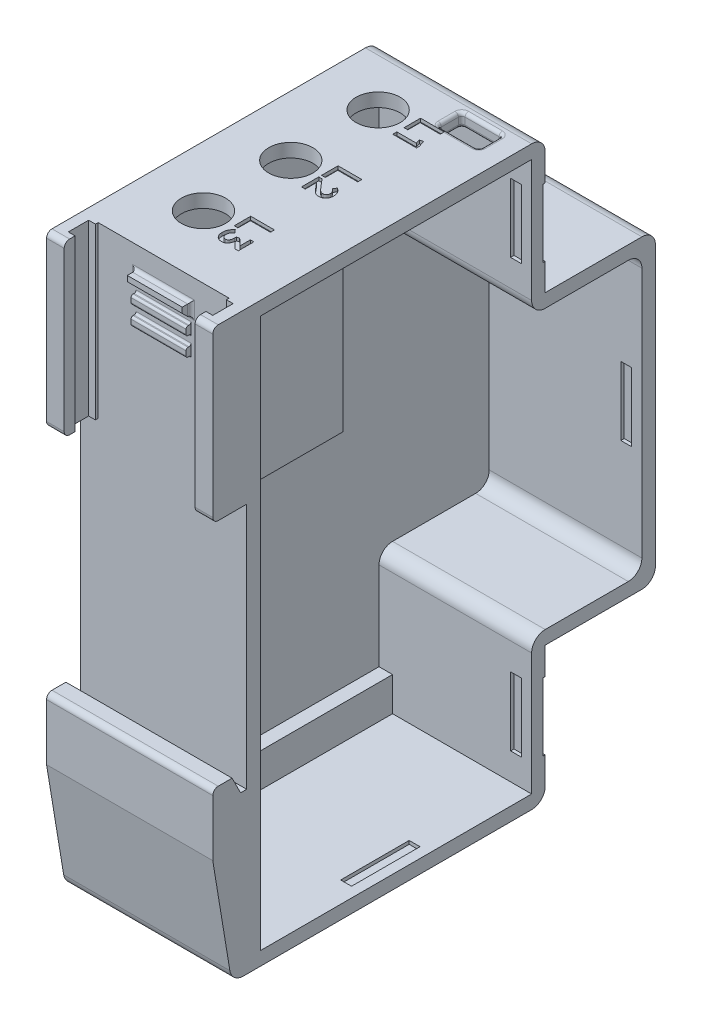
SolidWorks part; units mm, degrees
ref_plane "Front Plane" through (0, 0, 0) normal (0, 0, 1) x (1, 0, 0)
ref_plane "Top Plane" through (0, 0, 0) normal (0, 1, 0) x (1, 0, 0)
ref_plane "Right Plane" through (0, 0, 0) normal (1, 0, 0) x (0, 0, -1)
sketch "Sketch1" plane through (0, 0, 0) normal (1, 0, 0) x (0, 0, -1)
  line L0 (44, 65) -> (44, 85)
  line L1 (0, 0) -> (44, 0)
  line L2 (0, 0) -> (0, 85)
  line L3 (0, 85) -> (44, 85)
  line L4 (44, 0) -> (44, 20)
  line L5 (44, 65) -> (60.25, 65)
  line L7 (44, 20) -> (60.25, 20)
  line L8 (60.25, 65) -> (60.25, 20)
  dimension "D1" = 85
  dimension "D2" = 44
  dimension "D3" = 20
  dimension "D4" = 20
  dimension "D5" = 60.25
extrude "Boss-Extrude1" add sketch "Sketch1" along normal blind 24.5
shell "Shell1" thickness 2
sketch "Sketch2" plane through (2, 0, 0) normal (1, 0, 0) x (0, 0, -1)
  line L0 (42, 2) -> (42, 22) construction
  line L1 (42, 7) -> (12, 7)
  line L2 (42, 7) -> (42, 2)
  line L3 (42, 2) -> (12, 2)
  line L4 (12, 7) -> (12, 2)
  line L5 (2, 2) -> (42, 2) construction
  dimension "D1" = 30
  dimension "D2" = 5
extrude "Boss-Extrude2" add sketch "Sketch2" along normal blind 2
sketch "Sketch4" plane through (0, 85, 0) normal (0, 1, 0) x (1, 0, 0)
  circle A0 centre (8.86, 9.265) radius 3 construction
  circle A1 centre (8.86, 22.14) radius 3 construction
  circle A2 centre (8.86, 35.015) radius 3 construction
  circle A3 centre (8.86, 9.265) radius 3 construction
  circle A4 centre (8.86, 22.14) radius 3 construction
  circle A5 centre (8.86, 35.015) radius 3 construction
  circle A6 centre (8.86, 35.015) radius 3.25
  circle A7 centre (8.86, 22.14) radius 3.25
  circle A8 centre (8.86, 9.265) radius 3.25
  dimension "D1" = 0.25
extrude "Cut-Extrude2" cut sketch "Sketch4" against normal up to next
sketch "Sketch5" plane through (2, 0, 0) normal (1, 0, 0) x (0, 0, -1)
  line L0 (34.67, 36.04) -> (34.67, 70.24) construction
  line L1 (34.67, 64.64) -> (7.67, 64.64)
  line L2 (34.67, 64.64) -> (34.67, 41.64)
  line L3 (34.67, 41.64) -> (7.67, 41.64)
  line L4 (7.67, 64.64) -> (7.67, 41.64)
  line L5 (14.67, 70.24) -> (14.67, 36.04) construction
  point P6 (14.67, 53.14)
  point P9 (7.67, 53.14)
  dimension "D1" = 23
  dimension "D2" = 27
extrude "Boss-Extrude3" add sketch "Sketch5" along normal blind 2
sketch "Sketch6" plane through (24.5, 0, 0) normal (1, 0, 0) x (0, 0, -1)
  line L0 (0, 0) -> (-2.2, 0)
  line L1 (-2.2, 0) -> (-5, 17)
  line L2 (-5, 17) -> (-5, 26.1)
  line L3 (-5, 26.1) -> (-2.15, 26.1)
  line L4 (-2.15, 26.1) -> (-0.9, 23.6)
  line L5 (-0.9, 23.6) -> (0, 23.6)
  line L6 (0, 85) -> (0, 0) construction
  line L7 (0, 42.5) -> (-14.1034, 42.5) construction
  line L8 (0, 0) -> (44, 0) construction
  line L9 (0, 23.6) -> (0, 0)
  line L11 (44, 20) -> (58.25, 20) construction
  dimension "D1" = 5
  dimension "D2" = 6.1
  dimension "D3" = 17
  dimension "D4" = 2.2
  dimension "D5" = 2.5
  dimension "D6" = 0.9
  dimension "D7" = 2.15
extrude "Boss-Extrude4" add sketch "Sketch6" against normal up to surface (24.5 mm away) up to face at (0, 42.5, -37.0625)
sketch "Sketch7" plane through (0, 0, 0) normal (0, 0, 1) x (1, 0, 0)
  line L1 (24.5, 85) -> (21.9, 85)
  line L2 (24.5, 85) -> (24.5, 60)
  line L3 (24.5, 60) -> (21.9, 60)
  line L4 (21.9, 85) -> (21.9, 60)
  line L5 (12.25, 85) -> (12.25, 51.0538) construction
  line L6 (24.5, 85) -> (0, 85) construction
  line L7 (0, 60) -> (2.6, 60)
  line L8 (2.6, 85) -> (2.6, 60)
  line L9 (0, 85) -> (2.6, 85)
  line L10 (0, 85) -> (0, 60)
  line L11 (24.5, 65) -> (0, 65) construction
  dimension "D1" = 5
  dimension "D2" = 2.6
  dimension "D3" = 25
extrude "Boss-Extrude5" add sketch "Sketch7" along normal up to surface (5 mm away) up to face at (12.25, 21.55, 5)
sketch "Sketch8" plane through (0, 85, 0) normal (0, 1, 0) x (1, 0, 0)
  line L0 (21.9, 0) -> (2.6, 0) construction
  line L1 (22.9, -3.4) -> (1.6, -3.4)
  line L2 (22.9, -3.4) -> (22.9, -0.4)
  line L3 (22.9, -0.4) -> (1.6, -0.4)
  line L4 (1.6, -3.4) -> (1.6, -0.4)
  line L5 (2.6, -5) -> (2.6, 0) construction
  line L6 (21.9, -5) -> (21.9, 0) construction
  line L7 (24.5, -5) -> (21.9, -5) construction
  point P6 (12.25, 0)
  point P7 (12.25, -0.4)
  dimension "D1" = 0.4
  dimension "D2" = 1
  dimension "D3" = 1
  dimension "D4" = 1.6
extrude "Cut-Extrude3" cut sketch "Sketch8" against normal up to next
fillet "Fillet1" radius 2 9 edges at (12.25, 0, 2.2) (12.25, 85, -44) (12.25, 65, -60.25) (12.25, 20, -60.25) (12.25, 0, -44) (13.25, 63, -42) (13.25, 22, -42) (13.25, 63, -58.25) (13.25, 22, -58.25)
fillet "Fillet2" radius 0.8 5 edges at (12.25, 26.1, 5) (1.3, 60, 5) (23.2, 60, 5) (1.3, 85, 5) (23.2, 85, 5)
sketch "Sketch9" plane through (0, 85, 0) normal (0, 1, 0) x (1, 0, 0)
  line L0 (24.5, 42) -> (24.5, -4.2) construction
  line L1 (21.2, 41) -> (15.2, 41)
  line L2 (21.2, 41) -> (21.2, 37.5)
  line L3 (21.2, 37.5) -> (15.2, 37.5)
  line L4 (15.2, 41) -> (15.2, 37.5)
  line L5 (24.5, 42) -> (2, 42) construction
  dimension "D1" = 6
  dimension "D2" = 3.5
  dimension "D3" = 3.3
  dimension "D4" = 1
extrude "Cut-Extrude4" cut sketch "Sketch9" against normal up to next contours L2 L3 L4 L1
fillet "Fillet3" radius 0.5 12 edges at (18.2, 85, -37.5) (18.2, 83, -37.5) (18.2, 83, -41) (18.2, 85, -41) (21.2, 84, -41) (21.2, 85, -39.25) (21.2, 84, -37.5) (21.2, 83, -39.25) (15.2, 83, -39.25) (15.2, 84, -37.5) (15.2, 85, -39.25) (15.2, 84, -41)
sketch "Sketch10" plane through (0, 0, 0) normal (0, 0, 1) x (1, 0, 0)
  line L1 (16.3, 81.7) -> (8.2, 81.7)
  line L2 (16.3, 81.7) -> (16.3, 80.1)
  line L3 (16.3, 80.1) -> (8.2, 80.1)
  line L4 (8.2, 81.7) -> (8.2, 80.1)
  line L5 (21.9, 85) -> (2.6, 85) construction
  line L7 (16.5, 88.2) -> (16.5, 86.6) construction
  line L8 (18.1, 77.9) -> (6.4, 77.9) construction
  point P6 (12.25, 80.1)
  point P9 (12.25, 85)
  dimension "D1" = 2.2
  dimension "D2" = 1.6
  dimension "D3" = 0.2
extrude "Boss-Extrude6" add sketch "Sketch10" along normal offset from surface (1.3 mm away) 0.3
fillet "Fillet4" radius 0.5 4 edges at (16.3, 80.9, 0) (8.2, 80.9, 0) (12.25, 81.7, 0) (12.25, 80.1, 0)
sketch "Sketch12" plane through (0, 0, 0) normal (0, 0, 1) x (1, 0, 0)
  line L0 (6.4, 75.9) -> (18.1, 75.9) construction
  line L1 (18.1, 77.9) -> (6.4, 77.9) construction
  line L2 (8.2, 75.9) -> (16.3, 75.9) construction
  line L3 (16.3, 77.9) -> (8.2, 77.9) construction
  line L4 (16.3, 80.1) -> (16.3, 81.7) construction
  line L5 (16.3, 77.9) -> (8.2, 77.9) construction
  line L6 (16.3, 77.65) -> (16.3, 78.9)
  line L7 (16.3, 78.9) -> (8.2, 78.9)
  line L8 (8.2, 77.65) -> (8.2, 78.9)
  line L9 (16.3, 75.9) -> (8.2, 75.9) construction
  line L10 (16.3, 76.15) -> (16.3, 74.9)
  line L11 (16.3, 74.9) -> (8.2, 74.9)
  line L12 (8.2, 76.15) -> (8.2, 74.9)
  line L13 (8.2, 81.7) -> (8.2, 80.1) construction
  line L14 (16.3, 77.65) -> (8.2, 77.65)
  line L15 (8.2, 76.15) -> (16.3, 76.15)
  dimension "D1" = 1
  dimension "D2" = 1
  dimension "D3" = 0.25
extrude "Boss-Extrude7" add sketch "Sketch12" along normal blind 0.75 contours L8 L3 L6 L7 | L2 L12 L11 L10
fillet "Fillet5" radius 0.3 8 edges at (12.25, 78.9, 0) (12.25, 74.9, 0) (12.25, 74.9, 0.75) (12.25, 78.9, 0.75) (12.25, 76.15, 0) (12.25, 76.15, 0.75) (12.25, 77.65, 0) (12.25, 77.65, 0.75)
chamfer "Chamfer1" distance 0.8 angle 45 1 edges at (12.25, 80.1, 1.3)
sketch "Sketch13" plane through (0, 0, -44) normal (0, 0, -1) x (-1, 0, 0)
  line L0 (-24.5, 2) -> (-24.5, 20) construction
  line L1 (-24.5, 6) -> (-22.5, 6)
  line L2 (-24.5, 6) -> (-24.5, 16)
  line L3 (-24.5, 16) -> (-22.5, 16)
  line L4 (-22.5, 6) -> (-22.5, 16)
  line L5 (0, 2) -> (0, 20) construction
  line L6 (-12.25, 2) -> (-12.25, 83) construction
  line L7 (-24.5, 2) -> (0, 2) construction
  line L8 (0, 83) -> (-24.5, 83) construction
  line L9 (-12.25, 42.5) -> (-31.0931, 42.5) construction
  line L10 (-24.5, 69) -> (-22.5, 69)
  line L11 (-22.5, 79) -> (-22.5, 69)
  line L12 (-24.5, 79) -> (-22.5, 79)
  line L13 (-24.5, 79) -> (-24.5, 69)
  point P6 (-22.5, 11)
  point P9 (0, 11)
  dimension "D1" = 10
  dimension "D2" = 2
extrude "Cut-Extrude5" cut sketch "Sketch13" against normal blind 0.3
sketch "Sketch14" plane through (0, 0, -58.25) normal (0, 0, 1) x (1, 0, 0)
  line L0 (24.5, 24) -> (24.5, 61) construction
  line L1 (23, 47.55) -> (21.4, 47.55)
  line L2 (23, 47.55) -> (23, 37.45)
  line L3 (23, 37.45) -> (21.4, 37.45)
  line L4 (21.4, 47.55) -> (21.4, 37.45)
  point P6 (24.5, 42.5)
  point P7 (23, 42.5)
  dimension "D1" = 10.1
  dimension "D2" = 1.6
  dimension "D3" = 1.5
extrude "Cut-Extrude6" cut sketch "Sketch14" against normal blind 0.5
sketch "Sketch15" plane through (0, 0, -42) normal (0, 0, 1) x (1, 0, 0)
  line L1 (23, 79.05) -> (21.4, 79.05)
  line L2 (23, 79.05) -> (23, 68.95)
  line L3 (23, 68.95) -> (21.4, 68.95)
  line L4 (21.4, 79.05) -> (21.4, 68.95)
  line L5 (24.5, 65) -> (24.5, 83) construction
  line L6 (24.5, 83) -> (24.5, 2) construction
  line L7 (24.5, 42.5) -> (11.011, 42.5) construction
  line L8 (23, 16.05) -> (21.4, 16.05)
  line L9 (21.4, 5.95) -> (21.4, 16.05)
  line L10 (23, 5.95) -> (21.4, 5.95)
  line L11 (23, 5.95) -> (23, 16.05)
  point P6 (24.5, 74)
  point P7 (23, 74)
  dimension "D1" = 10.1
  dimension "D2" = 1.6
  dimension "D3" = 1.5
extrude "Cut-Extrude7" cut sketch "Sketch15" against normal blind 0.5
sketch "Sketch16" plane through (0, 2, 2) normal (0, 1, 0) x (1, 0, 0)
  line L1 (23, 29.05) -> (21.4, 29.05)
  line L2 (23, 29.05) -> (23, 18.95)
  line L3 (23, 18.95) -> (21.4, 18.95)
  line L4 (21.4, 29.05) -> (21.4, 18.95)
  line L5 (24.5, 4) -> (24.5, 44) construction
  point P6 (24.5, 24)
  point P7 (23, 24)
  dimension "D1" = 10.1
  dimension "D2" = 1.6
  dimension "D3" = 1.5
extrude "Cut-Extrude8" cut sketch "Sketch16" against normal blind 0.5
sketch "Sketch17" plane through (11.56, 83, -19.6102) normal (0, 1, 0) x (-1, 0, 0)
  line L1 (-9.84, 2.6602) -> (-11.44, 2.6602)
  line L2 (-9.84, 2.6602) -> (-9.84, -7.4398)
  line L3 (-9.84, -7.4398) -> (-11.44, -7.4398)
  line L4 (-11.44, 2.6602) -> (-11.44, -7.4398)
  line L5 (-12.94, -22.3898) -> (-12.94, 17.6102) construction
  point P4 (-11.44, -2.3898)
  point P8 (-12.94, -2.3898)
  dimension "D1" = 10.1
  dimension "D2" = 1.6
  dimension "D3" = 1.5
extrude "Cut-Extrude10" cut sketch "Sketch17" along normal blind 0.5
sketch "Sketch18" plane through (0, 0, -2) normal (0, 0, -1) x (-1, 0, 0)
  line L1 (-21.4, 57.6) -> (-23, 57.6)
  line L2 (-21.4, 57.6) -> (-21.4, 27.4)
  line L3 (-21.4, 27.4) -> (-23, 27.4)
  line L4 (-23, 57.6) -> (-23, 27.4)
  line L5 (-24.5, 83) -> (-24.5, 2) construction
  point P4 (-23, 42.5)
  point P8 (-24.5, 42.5)
  dimension "D1" = 30.2
  dimension "D2" = 1.6
  dimension "D3" = 1.5
extrude "Cut-Extrude11" cut sketch "Sketch18" against normal blind 0.5
sketch "Sketch19" plane through (0, 85, 0) normal (0, 1, 0) x (1, 0, 0)
  line L0 (13.0397, 38.265) -> (13.0397, 31.765) construction
  line L1 (8.86, 38.265) -> (13.0397, 38.265) construction
  line L2 (13.0397, 25.39) -> (13.0397, 18.89) construction
  line L3 (8.86, 31.765) -> (13.0397, 31.765) construction
  line L5 (8.86, 25.39) -> (13.0397, 25.39) construction
  line L6 (13.0397, 12.515) -> (13.0397, 6.015) construction
  line L7 (8.86, 18.89) -> (13.0397, 18.89) construction
  line L9 (8.86, 12.515) -> (13.0397, 12.515) construction
  line L11 (8.86, 6.015) -> (13.0397, 6.015) construction
  circle A0 centre (8.86, 35.015) radius 3.25 construction
  circle A1 centre (8.86, 22.14) radius 3.25 construction
  circle A2 centre (8.86, 9.265) radius 3.25 construction
  text T0 "L1"
  text T1 "L2"
  text T2 "L3"
extrude "Cut-Extrude12" cut sketch "Sketch19" against normal blind 0.5
sketch "Sketch20" plane through (0, 0, -60.25) normal (0, 0, -1) x (-1, 0, 0)
  line L0 (0, 36.4759) -> (-24.5, 36.4759) construction
  text T0 "<b>Smart</b>\r\n<b>&</b>\r\n<b>Simple</b>" font "Gotham" height 4.5
extrude "Boss-Extrude8" add sketch "Sketch20" along normal blind 0.5
